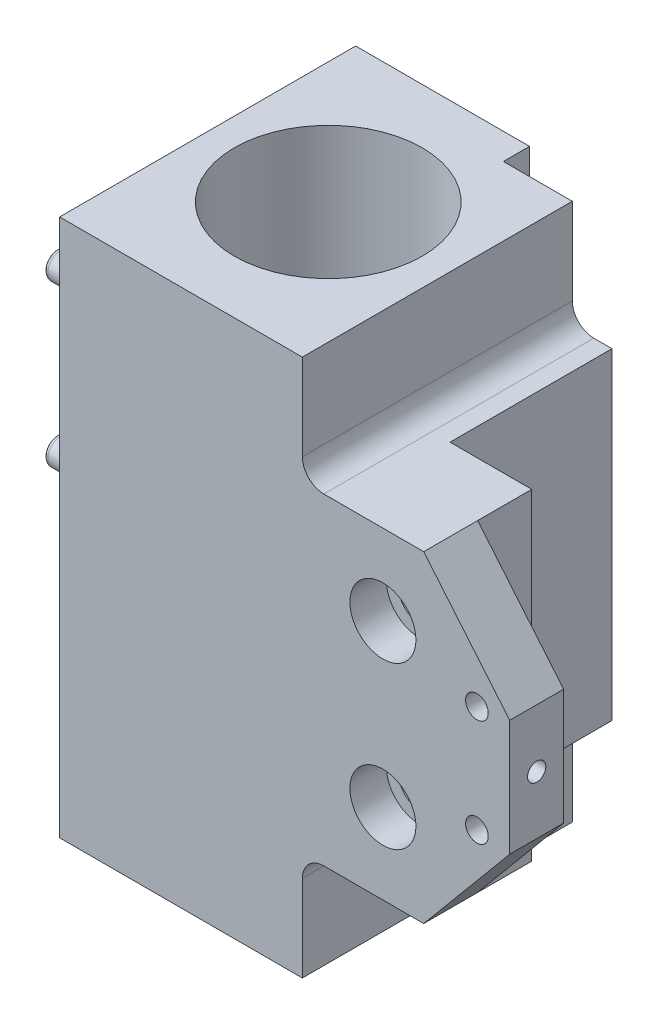
SolidWorks part; units mm, degrees
material "1060 Alloy"
ref_plane "Front Plane" through (0, 0, 0) normal (0, 0, 1) x (1, 0, 0)
ref_plane "Top Plane" through (0, 0, 0) normal (0, 1, 0) x (1, 0, 0)
ref_plane "Right Plane" through (0, 0, 0) normal (1, 0, 0) x (0, 0, -1)
sketch "Sketch1" plane through (0, 0, 0) normal (0, 1, 0) x (1, 0, 0)
  line L0 (-14.34, 17.58) -> (-14.34, -17.4)
  line L1 (-14.34, -17.4) -> (38.84, -17.4)
  line L2 (38.84, -17.4) -> (38.84, -11.03)
  line L3 (38.84, -11.03) -> (28.68, -11.03)
  line L4 (28.68, -11.03) -> (28.68, -4.64)
  line L5 (28.68, -4.64) -> (19.03, -4.64)
  line L6 (14.34, -4.64) -> (14.34, 14.49) construction
  line L7 (14.34, 14.49) -> (6.2, 14.49)
  line L8 (6.2, 14.49) -> (6.2, 17.58)
  line L9 (6.2, 17.58) -> (-14.34, 17.58)
  line L10 (0, 0) -> (0, 51.3699) construction
  line L11 (0, -11.1) -> (-14.34, -11.1) construction
  line L12 (14.34, 14.49) -> (19.03, 14.49)
  line L13 (19.03, 14.49) -> (19.03, -4.64)
  line L14 (14.34, -4.64) -> (19.03, -4.64) construction
  circle A0 centre (0, 0) radius 11.1
  dimension "D1" = 22.2
  dimension "D2" = 28.68
  dimension "D3" = 20.54
  dimension "D4" = 53.18
  dimension "D5" = 43.02
  dimension "D6" = 6.3
  dimension "D7" = 34.98
  dimension "D8" = 31.89
  dimension "D9" = 12.76
  dimension "D10" = 6.37
  dimension "D11" = 33.37
extrude "Boss-Extrude1" add sketch "Sketch1" along normal blind 31.765 and the other way blind 31.765
sketch "Sketch2" plane through (-14.34, 0, 0) normal (-1, 0, 0) x (0, 0, 1)
  line L0 (0, 0) -> (18.9221, 0) construction
  line L1 (-6.365, -19.06) -> (6.365, -19.06)
  line L2 (-6.365, -19.06) -> (-6.365, 19.06)
  line L3 (-6.365, 19.06) -> (6.365, 19.06)
  line L4 (6.365, -19.06) -> (6.365, 19.06)
  line L5 (0, 0) -> (0, -42.4085) construction
  dimension "D1" = 38.12
  dimension "D2" = 12.73
extrude "Boss-Extrude2" add sketch "Sketch2" along normal blind 9.43
sketch "Sketch3" plane through (0, 0, -17.58) normal (0, 0, -1) x (-1, 0, 0)
  line L0 (0, 0) -> (-38.84, 0) construction
  line L1 (-38.84, -31.765) -> (-38.84, 31.765) construction
  line L2 (-38.84, 6.85) -> (-28.68, 19.025)
  line L3 (-28.68, 19.025) -> (-16.88, 19.025)
  line L4 (-14.34, 21.565) -> (-14.34, 31.765)
  line L5 (-38.84, 6.85) -> (-38.84, 31.765)
  line L6 (-38.84, 31.765) -> (-14.34, 31.765)
  line L7 (-28.68, -19.025) -> (-16.88, -19.025)
  line L8 (-38.84, -31.765) -> (-14.34, -31.765)
  line L9 (-38.84, -6.85) -> (-38.84, -31.765)
  line L10 (-14.34, -21.565) -> (-14.34, -31.765)
  line L11 (-38.84, -6.85) -> (-28.68, -19.025)
  line L12 (-38.84, -6.85) -> (-38.84, 6.85) construction
  line L13 (-38.84, 31.765) -> (-28.68, 31.765) construction
  line L14 (-14.34, 21.565) -> (-14.34, -21.565) construction
  line L15 (-28.68, -31.765) -> (-28.68, 31.765) construction
  arc A0 (-16.88, 19.025) -> (-14.34, 21.565) centre (-16.88, 21.565) ccw
  arc A1 (-16.88, -19.025) -> (-14.34, -21.565) centre (-16.88, -21.565) cw
  dimension "D1" = 2.54
  dimension "D2" = 38.05
  dimension "D3" = 13.7
extrude "Cut-Extrude1" cut sketch "Sketch3" against normal through all
chamfer "Chamfer1" distance 1.6 angle 45 1 edges at (-23.77, -19.06, 0)
sketch "Sketch4" plane through (0, 0, -14.49) normal (0, 0, -1) x (-1, 0, 0)
  line L0 (0, 0) -> (-12.48, 0) construction
  line L1 (-13.89, 0) -> (-13.89, 7.9644) construction
  line L2 (-19.03, -19.025) -> (-19.03, 19.025) construction
  circle A0 centre (-12.48, 0) radius 1.41
  dimension "D1" = 2.82
  dimension "D2" = 5.14
extrude "Cut-Extrude2" cut sketch "Sketch4" against normal blind 11
sketch "Sketch5" plane through (0, 0, 4.64) normal (0, 0, -1) x (-1, 0, 0)
  line L0 (-23.855, -19.025) -> (-23.855, 19.025) construction
  line L1 (-19.03, -19.025) -> (-28.68, -19.025) construction
  line L2 (-28.68, 19.025) -> (-19.03, 19.025) construction
  line L3 (0, 0) -> (-49.0842, 0) construction
  line L4 (-23.855, 7.085) -> (-31.0346, 7.085) construction
  line L5 (-23.855, -7.085) -> (-34.1674, -7.085) construction
  circle A0 centre (-23.855, -9.53) radius 2.445
  circle A1 centre (-23.855, 9.53) radius 2.445
  dimension "D1" = 4.89
  dimension "D2" = 14.17
extrude "Cut-Extrude3" cut sketch "Sketch5" against normal through all
sketch "Sketch6" plane through (0, 0, 17.4) normal (0, 0, 1) x (1, 0, 0)
  circle A0 centre (23.855, -9.53) radius 3.9
  circle A1 centre (23.855, 9.53) radius 3.9
  dimension "D1" = 7.8
extrude "Cut-Extrude4" cut sketch "Sketch6" against normal blind 4.32
sketch "Sketch7" plane through (0, 0, 11.03) normal (0, 0, -1) x (-1, 0, 0)
  line L0 (0, 0) -> (-34.96, 0) construction
  line L1 (-34.96, 6.31) -> (-34.96, -6.31) construction
  line L2 (-34.96, 4.97) -> (-40.9332, 4.97) construction
  line L3 (-34.96, -4.97) -> (-40.9332, -4.97) construction
  line L4 (-36.3, 6.31) -> (-36.3, -6.31) construction
  line L5 (-38.84, -6.85) -> (-38.84, 6.85) construction
  circle A0 centre (-34.96, 6.31) radius 1.34
  circle A1 centre (-34.96, -6.31) radius 1.34
  dimension "D1" = 2.68
  dimension "D2" = 9.94
  dimension "D3" = 2.54
extrude "Cut-Extrude5" cut sketch "Sketch7" against normal through all
sketch "Sketch8" plane through (-23.77, 0, 0) normal (-1, 0, 0) x (0, 0, 1)
  circle A0 centre (0, 0) radius 2
  dimension "D1" = 4
extrude "Cut-Extrude6" cut sketch "Sketch8" against normal blind 10.5
sketch "Sketch9" plane through (-23.77, 0, 0) normal (-1, 0, 0) x (0, 0, 1)
  line L0 (0, -9.505) -> (0, 9.505) construction
  line L1 (0, 0) -> (-13.2131, 0) construction
  line L2 (0, -11.075) -> (2.7693, -11.075) construction
  line L3 (0, 11.075) -> (2.7693, 11.075) construction
  circle A0 centre (0, -9.505) radius 1.57
  circle A1 centre (0, 9.505) radius 1.57
  dimension "D2" = 3.14
  dimension "D1" = 22.15
extrude "Boss-Extrude3" add sketch "Sketch9" along normal blind 8.3
fillet "Fillet1" radius 0.5 2 edges at (-32.07, 9.505, 1.57) (-32.07, -9.505, 1.57)
sketch "Sketch10" plane through (38.84, 0, 0) normal (1, 0, 0) x (0, 0, -1)
  line L0 (-14.215, 0) -> (-17.4, 0) construction
  line L1 (-17.4, -6.85) -> (-17.4, 6.85) construction
  line L2 (-14.215, 0) -> (-14.215, -6.85) construction
  line L3 (-17.4, -6.85) -> (-11.03, -6.85) construction
  line L4 (-17.4, 6.85) -> (-11.03, 6.85) construction
  line L5 (-11.03, -6.85) -> (-11.03, 6.85) construction
  circle A0 centre (-14.215, 0) radius 1.075
  dimension "D1" = 2.15
extrude "Cut-Extrude7" cut sketch "Sketch10" against normal blind 6.35
